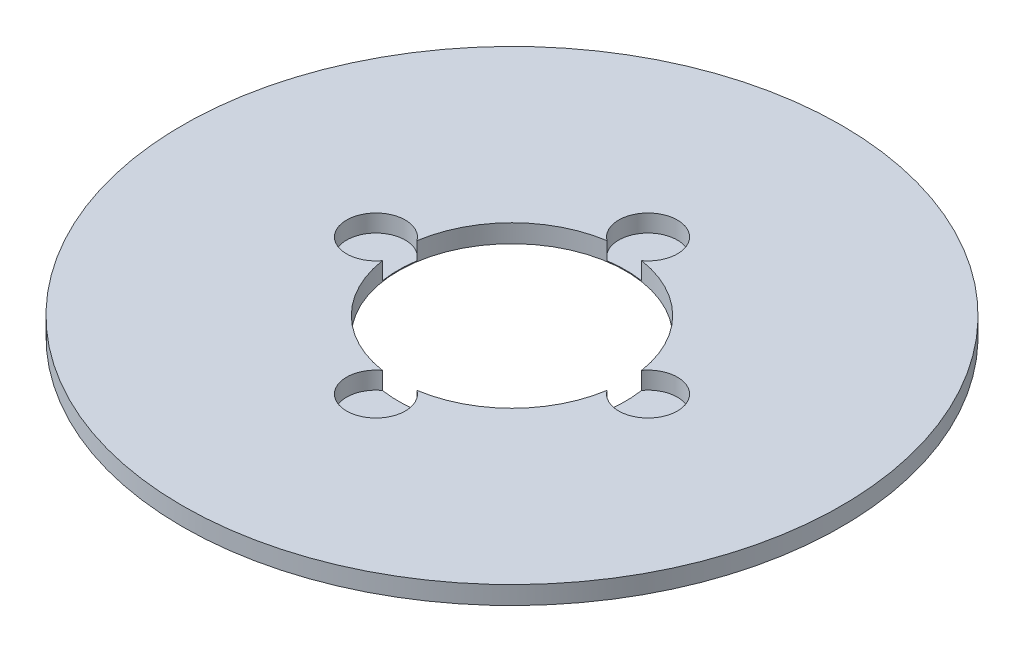
SolidWorks part; units mm, degrees
ref_plane "Front Plane" through (0, 0, 0) normal (0, 0, 1) x (1, 0, 0)
ref_plane "Top Plane" through (0, 0, 0) normal (0, 1, 0) x (1, 0, 0)
ref_plane "Right Plane" through (0, 0, 0) normal (1, 0, 0) x (0, 0, -1)
sketch "Sketch1" plane through (0, 0, 0) normal (0, 1, 0) x (1, 0, 0)
  circle A0 centre (0, 0) radius 72.5
  dimension "FLANGE_OD" = 145
extrude "Boss-Extrude1" add sketch "Sketch1" along normal blind 4
sketch "Sketch2" plane through (0, 0, 0) normal (0, 1, 0) x (1, 0, 0)
  circle A0 centre (0, 0) radius 25
  dimension "BORE_D" = 50
extrude "Cut-Extrude1" cut sketch "Sketch2" along normal through all
sketch "Sketch3" plane through (0, 4, 0) normal (0, 1, 0) x (1, 0, 0)
  circle A0 centre (0, 0) radius 29.9305 construction
  circle A1 centre (-29.9305, 0) radius 6.4603
  dimension "BOLT_D" = 12.9207
  dimension "BOLT_PCD" = 59.861
extrude "Cut-Extrude2" cut sketch "Sketch3" against normal blind 3.8261
pattern_circular "CirPattern1" count 4 over 360 about axis through (0, 0, 0) along (0, 1, 0) of "Cut-Extrude2"
